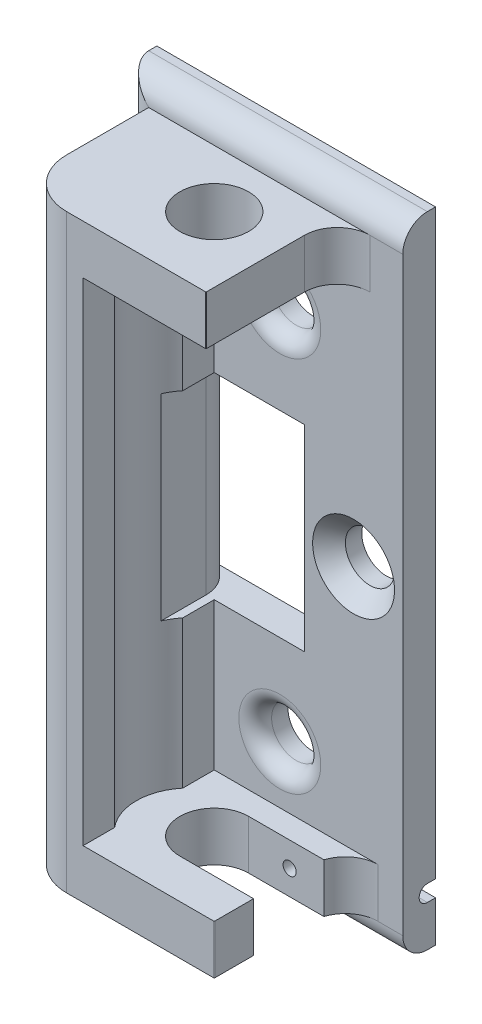
SolidWorks part; units mm, degrees
ref_plane "Plan de face" through (0, 0, 0) normal (0, 0, 1) x (1, 0, 0)
ref_plane "Plan de dessus" through (0, 0, 0) normal (0, 1, 0) x (1, 0, 0)
ref_plane "Plan de droite" through (0, 0, 0) normal (1, 0, 0) x (0, 0, -1)
sketch "Esquisse1" plane through (0, 0, 0) normal (0, 0, 1) x (1, 0, 0)
  line L1 (0, 0) -> (17, 0)
  line L2 (0, 0) -> (0, 39)
  line L3 (0, 39) -> (17, 39)
  line L4 (17, 0) -> (17, 39)
  dimension "D1" = 17
  dimension "D2" = 39
extrude "Boss.-Extru.1" add sketch "Esquisse1" along normal blind 2
sketch "Esquisse2" plane through (0, 0, 2) normal (0, 0, 1) x (1, 0, 0)
  line L0 (0, 39) -> (0, 0) construction
  line L1 (5, 37.5) -> (13, 37.5)
  line L2 (5, 37.5) -> (5, 34.5)
  line L3 (5, 34.5) -> (13, 34.5)
  line L4 (13, 37.5) -> (13, 34.5)
  line L5 (4.5, 4.5038) -> (13.5, 4.5038)
  line L6 (4.5, 4.5038) -> (4.5, 1.5038)
  line L7 (4.5, 1.5038) -> (13.5, 1.5038)
  line L8 (13.5, 4.5038) -> (13.5, 1.5038)
  line L9 (17, 39) -> (0, 39) construction
  point P8 (9, 37.5)
  point P11 (9, 4.5038)
  point P12 (9, 34.5)
  point P13 (5, 36)
  point P14 (4.5, 3.0038)
  dimension "D1" = 9
  dimension "D2" = 0
  dimension "D3" = 8
  dimension "D4" = 9
  dimension "D5" = 3
  dimension "D6" = 3
  dimension "D7" = 33
  dimension "D8" = 3
extrude "Boss.-Extru.2" add sketch "Esquisse2" along normal blind 8
sketch "Esquisse3" plane through (0, 1.5038, 0) normal (0, -1, 0) x (1, 0, 0)
  line L0 (4.5, 10) -> (13.5, 10) construction
  circle A0 centre (9, 5.5) radius 2.1
  point P4 (9, 10)
  dimension "D3" = 4.2
  dimension "D1" = 0
  dimension "D2" = 4.5
extrude "Enlèv. mat.-Extru.1" cut sketch "Esquisse3" against normal through all
fillet "Congé1" radius 0.0326 2 edges at (13.5, 3.0038, 10) (13, 36, 10)
sketch "Esquisse14" plane through (0, 0, 2) normal (0, 0, 1) x (1, 0, 0)
  line L0 (12.9674, 37.5) -> (5, 37.5) construction
  line L1 (1.5, 37.5) -> (5.5, 37.5)
  line L2 (1.5, 37.5) -> (1.5, 1.5038)
  line L3 (1.5, 1.5038) -> (5.5, 1.5038)
  line L4 (5.5, 37.5) -> (5.5, 1.5038)
  line L5 (4.5, 1.5038) -> (13.4674, 1.5038) construction
  line L6 (0, 39) -> (0, 0) construction
  dimension "D1" = 0
  dimension "D2" = 0
  dimension "D3" = 4
  dimension "D4" = 1.5
extrude "Boss.-Extru.8" add sketch "Esquisse14" along normal blind 8
sketch "Esquisse4" plane through (0, 0, 2) normal (0, 0, 1) x (1, 0, 0)
  line L0 (0, 39) -> (0, 0) construction
  line L1 (5, 25.5) -> (11, 25.5)
  line L2 (5, 25.5) -> (5, 13.5)
  line L3 (5, 13.5) -> (11, 13.5)
  line L4 (11, 25.5) -> (11, 13.5)
  line L10 (13.5, 4.5038) -> (5.5, 4.5038) construction
  line L12 (5.5, 34.5) -> (12.9674, 34.5) construction
  point P6 (0, 19.5)
  point P7 (5, 19.5)
  dimension "D1" = 5
  dimension "D2" = 6
  dimension "D3" = 0
  dimension "D4" = 12
  dimension "D5" = 14.9962
  dimension "D6" = 15
extrude "Enlèv. mat.-Extru.2" cut sketch "Esquisse4" against normal through all and the other way blind 3
sketch "Esquisse15" plane through (0, 1.5038, 0) normal (0, -1, 0) x (1, 0, 0)
  line L0 (1.5, 2) -> (13.5, 2) construction
  line L1 (1.5, 10) -> (1.5, 2) construction
  circle A0 centre (8, 6) radius 3.25
  point P7 (1.5, 6)
  dimension "D1" = 6.5
  dimension "D2" = 4
  dimension "D3" = 6.5
extrude "Enlèv. mat.-Extru.7" cut sketch "Esquisse15" against normal blind 29.95 from offset 3 offset against normal yes
fillet "Congé9" radius 3 1 edges at (1.5, 19.5019, 10)
fillet "Congé10" radius 2 1 edges at (5, 19.5, 0)
fillet "Congé11" radius 2 2 edges at (13, 36, 2) (13.5, 3.0038, 2)
fillet "Congé12" radius 1.5 3 edges at (8.5, 39, 2) (0, 19.5, 2) (8.5, 0, 2)
sketch "Esquisse16" plane through (0, 0, 0) normal (0, 0, -1) x (-1, 0, 0)
  line L0 (0, 39) -> (0, 0) construction
  line L1 (-17, 39) -> (0, 39) construction
  line L2 (0, 0) -> (-17, 0) construction
  circle A0 centre (-3.5, 35.5) radius 1
  circle A1 centre (-3.5, 3.5) radius 1
  dimension "D1" = 2
  dimension "D2" = 2
  dimension "D3" = 3.5
  dimension "D4" = 3.5
  dimension "D5" = 3.5
  dimension "D6" = 3.5
extrude "Enlèv. mat.-Extru.8" cut sketch "Esquisse16" against normal blind 8
fillet "Congé13" [suppressed] radius 1.5 tangent propagation no
sketch "Esquisse17" plane through (0, 1.5038, 0) normal (0, -1, 0) x (1, 0, 0)
  line L1 (9, 7.6) -> (15.2988, 7.6)
  line L2 (9, 7.6) -> (9, 3.4)
  line L3 (9, 3.4) -> (15.2988, 3.4)
  line L4 (15.2988, 7.6) -> (15.2988, 3.4)
  circle A0 centre (9, 5.5) radius 2.1 construction
  point P6 (0, 0)
  dimension "D1" = 4.2
extrude "Enlèv. mat.-Extru.9" cut sketch "Esquisse17" against normal up to next
sketch "Esquisse18" plane through (0, 0, 10) normal (0, 0, 1) x (1, 0, 0)
  line L0 (13.5921, 1.5038) -> (13.5921, 4.5038) construction
  line L1 (9, 4.5038) -> (9, 1.5038) construction
  circle A0 centre (11.5, 3.0038) radius 0.4
  point P4 (13.5921, 3.0038)
  point P7 (9, 3.0038)
  dimension "D1" = 0
  dimension "D3" = 0.8
  dimension "D2" = 2.5
extrude "Enlèv. mat.-Extru.10" cut sketch "Esquisse18" against normal blind 10 from offset 0.5 offset against normal yes
sketch "Esquisse19" [suppressed] plane through (18, 0, 0) normal (1, 0, 0) x (0, 0, -1)
  line L0 (-7.992, 4.5341) -> (-7.992, 1.5341) construction
  line L1 (0, 0) -> (0, 39) construction
  circle A0 centre (-0.45, 3.0341) radius 0.45
  point P4 (-7.992, 3.0341)
  dimension "D1" = 0.9
  dimension "D2" = 0
  dimension "D3" = 0.45
sketch "Esquisse20" plane through (17, 0, 0) normal (1, 0, 0) x (0, 0, -1)
  line L0 (-0.5, 3.0038) -> (1.0409, 3.0038) construction
  line L1 (-0.5, 3.5038) -> (1.0409, 3.5038)
  line L2 (-0.5, 2.5038) -> (1.0409, 2.5038)
  line L3 (-7.6, 4.5038) -> (-7.6, 1.5038) construction
  line L5 (0, 0) -> (0, 39) construction
  arc A0 (-0.5, 3.5038) -> (-0.5, 2.5038) centre (-0.5, 3.0038) ccw
  arc A1 (1.0409, 2.5038) -> (1.0409, 3.5038) centre (1.0409, 3.0038) ccw
  point P2 (0.2704, 3.0038)
  point P9 (-7.6, 3.0038)
  dimension "D1" = 0.5
  dimension "D2" = 0
  dimension "D3" = 0.5
extrude "Enlèv. mat.-Extru.18" cut sketch "Esquisse20" against normal blind 7
sketch "Esquisse21" plane through (0, 0, 2) normal (0, 0, 1) x (1, 0, 0)
  line L0 (17, 1.5) -> (17, 37.5) construction
  circle A0 centre (14, 19.5) radius 1.5
  point P4 (17, 19.5)
  dimension "D1" = 0
  dimension "D2" = 3
  dimension "D3" = 3
extrude "Enlèv. mat.-Extru.19" cut sketch "Esquisse21" against normal through all
chamfer "Chanfrein1" distance 1 angle 45 1 edges at (15.5, 19.5, 2)
sketch "Esquisse22" plane through (0, 0, 2) normal (0, 0, 1) x (1, 0, 0)
  line L0 (5.5, 4.5038) -> (5.5, 34.5) construction
  line L1 (5.5, 34.5) -> (12.9674, 34.5) construction
  line L2 (13.4674, 4.5038) -> (5.5, 4.5038) construction
  circle A0 centre (9.5, 31) radius 1.5
  circle A1 centre (9.5, 8.0038) radius 1.5
  dimension "D1" = 4
  dimension "D2" = 3
  dimension "D3" = 3
  dimension "D4" = 3.5
  dimension "D5" = 3.5
extrude "Enlèv. mat.-Extru.20" cut sketch "Esquisse22" against normal up to next
fillet "Congé14" radius 1 2 edges at (11, 8.0038, 2) (11, 31, 2)
